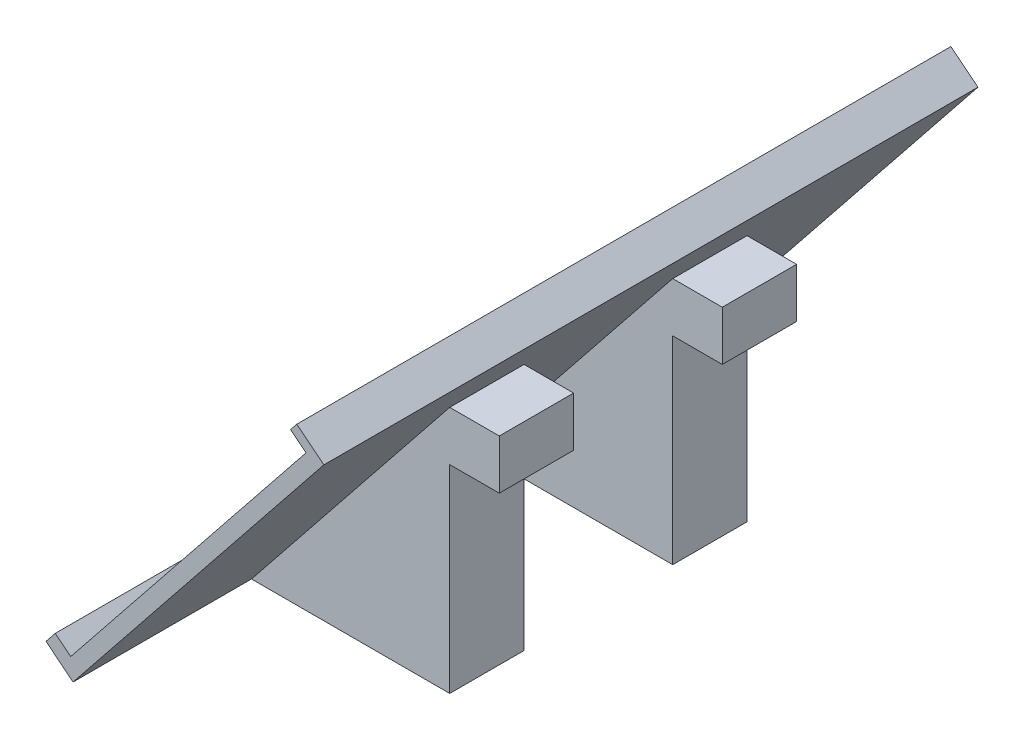
SolidWorks part; units mm, degrees
ref_plane "Alzado" through (0, 0, 0) normal (0, 0, 1) x (1, 0, 0)
ref_plane "Planta" through (0, 0, 0) normal (0, 1, 0) x (1, 0, 0)
ref_plane "Vista lateral" through (0, 0, 0) normal (1, 0, 0) x (0, 0, -1)
sketch "Croquis1" plane through (0, 0, 0) normal (0, 0, 1) x (1, 0, 0)
  line L0 (-20, 0) -> (20, 0)
  line L1 (20, 0) -> (20, 50)
  line L2 (20, 50) -> (-20, 0)
  dimension "D1" = 50
  dimension "D2" = 40
extrude "Saliente-Extruir1" add sketch "Croquis1" along normal blind 60
sketch "Croquis2" plane through (-12.1951, 9.7561, 0) normal (-0.7809, 0.6247, 0) x (0, 0, 1)
  line L0 (60, 51.5373) -> (0, 51.5373) construction
  line L1 (15, 51.5373) -> (45, 51.5373)
  line L2 (15, 51.5373) -> (15, -12.4939)
  line L3 (15, -12.4939) -> (45, -12.4939)
  line L4 (45, 51.5373) -> (45, -12.4939)
  line L5 (60, -12.4939) -> (0, -12.4939) construction
  line L6 (0, 51.5373) -> (0, -12.4939) construction
  line L7 (60, 51.5373) -> (60, -12.4939) construction
  dimension "D1" = 15
  dimension "D2" = 15
extrude "Cortar-Extruir1" cut sketch "Croquis2" against normal up to next
sketch "Croquis3" plane through (-12.1951, 9.7561, 0) normal (-0.7809, 0.6247, 0) x (0, 0, 1)
  line L0 (15, -12.4939) -> (0, -12.4939) construction
  line L1 (-36, 68.5061) -> (96, 68.5061)
  line L2 (-36, 68.5061) -> (-36, -12.4939)
  line L3 (-36, -12.4939) -> (96, -12.4939)
  line L4 (96, 68.5061) -> (96, -12.4939)
  line L7 (30, 68.5061) -> (30, -12.4939) construction
  line L8 (0, 51.5373) -> (0, -12.4939) construction
  point P12 (30, 68.5061)
  dimension "D1" = 132
  dimension "D2" = 81
  dimension "D3" = 30
extrude "Saliente-Extruir2" add sketch "Croquis3" along normal blind 3
sketch "Croquis4" plane through (20, 0, 0) normal (1, 0, 0) x (0, 0, -1)
  line L0 (-45, 0) -> (-45, 50) construction
  line L1 (-60, 50) -> (-45, 50)
  line L2 (-60, 50) -> (-60, 40)
  line L3 (-60, 40) -> (-45, 40)
  line L4 (-45, 50) -> (-45, 40)
  line L5 (0, 50) -> (0, 0) construction
  line L6 (-15, 50) -> (0, 50)
  line L7 (-15, 50) -> (-15, 40)
  line L8 (-15, 40) -> (0, 40)
  line L9 (0, 50) -> (0, 40)
  dimension "D1" = 10
  dimension "D2" = 10
extrude "Saliente-Extruir3" add sketch "Croquis4" along normal blind 10
sketch "Croquis5" plane through (-14.5377, 11.6302, 0) normal (-0.7809, 0.6247, 0) x (0, 0, 1)
  line L0 (96, -12.4939) -> (96, 68.5061) construction
  line L1 (-36, 68.5061) -> (96, 68.5061)
  line L2 (-36, 68.5061) -> (-36, 66.5061)
  line L3 (-36, 66.5061) -> (96, 66.5061)
  line L4 (96, 68.5061) -> (96, 66.5061)
  line L5 (-36, 68.5061) -> (-36, -12.4939) construction
  line L6 (-36, -9.4939) -> (96, -9.4939)
  line L7 (-36, -9.4939) -> (-36, -12.4939)
  line L8 (-36, -12.4939) -> (96, -12.4939)
  line L9 (96, -9.4939) -> (96, -12.4939)
  dimension "D1" = 3
  dimension "D2" = 2
extrude "Saliente-Extruir4" add sketch "Croquis5" along normal blind 4
